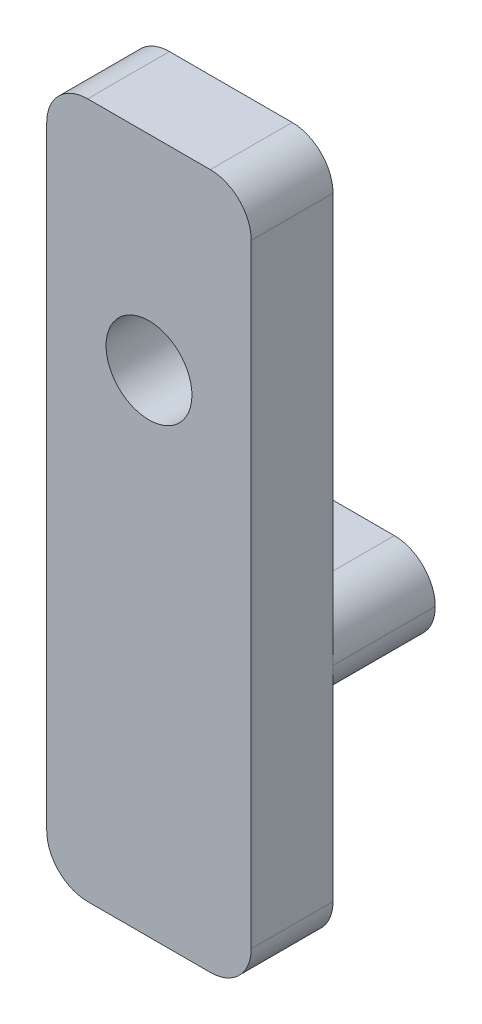
SolidWorks part; units mm, degrees
ref_plane "Спереди" through (0, 0, 0) normal (0, 0, 1) x (1, 0, 0)
ref_plane "Сверху" through (0, 0, 0) normal (0, 1, 0) x (1, 0, 0)
ref_plane "Справа" through (0, 0, 0) normal (1, 0, 0) x (0, 0, -1)
sketch "Эскиз1" plane through (0, 0, 0) normal (1, 0, 0) x (0, 0, -1)
  line L0 (0, 0) -> (0, 24)
  line L1 (0, 24) -> (4, 24)
  line L2 (4, 24) -> (4, 4)
  line L3 (4, 4) -> (9, 4)
  line L4 (9, 4) -> (9, 0)
  line L5 (9, 0) -> (4, 0)
  line L6 (4, 0) -> (4, -10)
  line L7 (4, -10) -> (0, -10)
  line L8 (0, -10) -> (0, 0)
  dimension "D1" = 20
  dimension "D2" = 4
  dimension "D3" = 5
  dimension "D4" = 4
  dimension "D5" = 4
  dimension "D6" = 10
extrude "Бобышка-Вытянуть1" add sketch "Эскиз1" along normal mid plane 10
fillet "Скругление1" radius 2 8 edges at (-5, 0, -6.5) (-5, 4, -6.5) (5, 4, -6.5) (5, 0, -6.5) (5, 24, -2) (-5, 24, -2) (-5, -10, -2) (5, -10, -2)
sketch "Эскиз2" plane through (0, 0, -4) normal (0, 0, -1) x (-1, 0, 0)
  line L0 (0, 24) -> (0, 4) construction
  line L1 (-3, 24) -> (3, 24) construction
  line L2 (-3, 4) -> (3, 4) construction
  circle A0 centre (0, 14) radius 2.1
  dimension "D1" = 4.2
extrude "Вырез-Вытянуть1" cut sketch "Эскиз2" against normal through all
